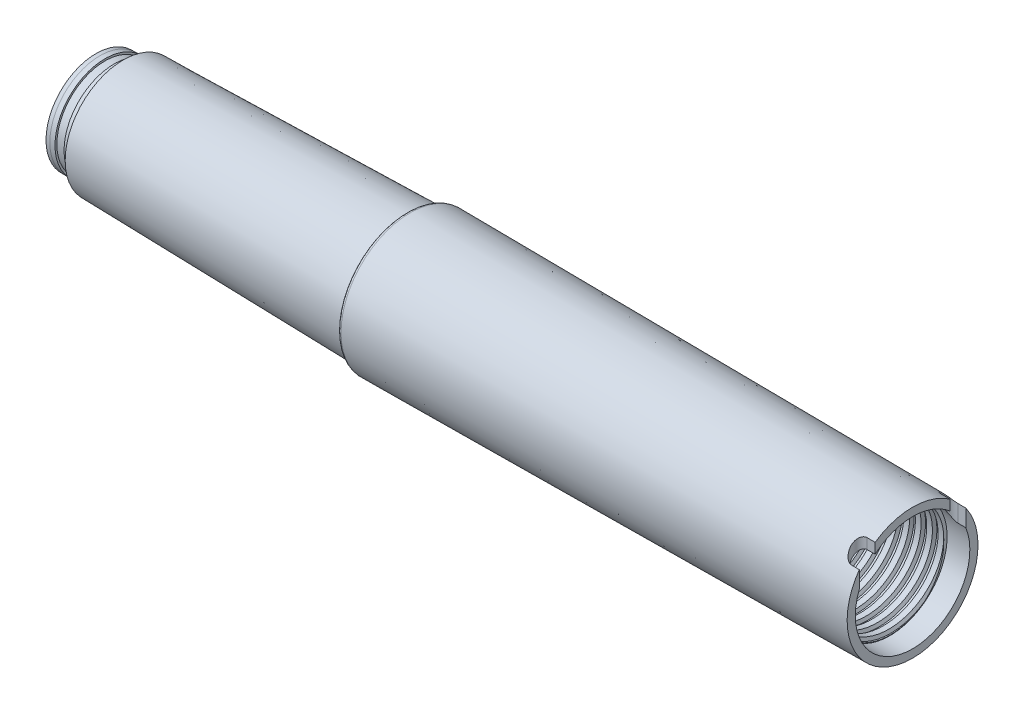
SolidWorks part; units mm, degrees
material "3.0205 (EN-AW 1200)"
ref_plane "Plano frontal" through (0, 0, 0) normal (0, 0, 1) x (1, 0, 0)
ref_plane "Plano superior" through (0, 0, 0) normal (0, 1, 0) x (1, 0, 0)
ref_plane "Plano direito" through (0, 0, 0) normal (1, 0, 0) x (0, 0, -1)
sketch "Esboço1" plane through (0, 0, 0) normal (0, 0, 1) x (1, 0, 0)
  line L0 (0, 0) -> (72, 0) construction
  line L1 (70, -4.75) -> (60, -4.75)
  line L2 (60, -4.75) -> (3, -4.75)
  line L3 (70, -4.75) -> (70, -5.05)
  line L4 (70, -5.05) -> (72, -5.05)
  line L5 (0, -3.45) -> (0.2, -3.25)
  line L6 (72, -5.77) -> (27.7022, -6.1)
  line L7 (27.4, -5.65) -> (27.4, -5.8)
  line L8 (2.4, -5.12) -> (27.4, -5.65)
  line L17 (3, -3.5387) -> (3, -4.75)
  line L18 (0, -4.41) -> (0.35, -4.42)
  line L19 (72, -5.77) -> (72, -5.05)
  line L21 (2.5, -3.25) -> (3, -3.5387)
  line L22 (0.2, -3.25) -> (2.5, -3.25)
  line L24 (2.4, -4.42) -> (2.4, -5.12)
  line L25 (1.6, -4.42) -> (2.4, -4.42)
  line L26 (1.6, -4.25) -> (1.6, -4.42)
  line L27 (0.8, -4.25) -> (1.6, -4.25)
  line L28 (0.8, -4.42) -> (0.8, -4.25)
  line L29 (0.35, -4.42) -> (0.8, -4.42)
  line L30 (0, -3.45) -> (0, -4.41)
  arc A0 (27.7022, -6.1) -> (27.4, -5.8) centre (27.7, -5.8) cw
  point P18 (27.4, -5.65)
  point P30 (0, -3.25)
  dimension "D19" = 0.3
  dimension "D29" = 10.24
  dimension "D2" = 11.54
  dimension "D3" = 72
  dimension "D4" = 6.5
  dimension "D5" = 8.82
  dimension "D6" = 8.84
  dimension "D7" = 0.35
  dimension "D8" = 0.8
  dimension "D9" = 0.8
  dimension "D10" = 2.4
  dimension "D11" = 3
  dimension "D12" = 8.5
  dimension "D13" = 12
  dimension "D14" = 30
  dimension "D15" = 0.5
  dimension "D16" = 0.9
  dimension "D17" = 11.3
  dimension "D18" = 9.5
  dimension "D20" = 2
  dimension "D21" = 10.1
  dimension "D22" = 27.4
  dimension "D23" = 0.2
  dimension "D24" = 45
  dimension "D25" = 12.2
  dimension "D27" = 9.5
  dimension "D28" = 0.3826
revolve "Revolução1" add sketch "Esboço1" angle 360 about L0
sketch "Esboço7" plane through (0, 0, 0) normal (0, 1, 0) x (1, 0, 0)
  line L0 (0, 0) -> (74.2533, 0) construction
  line L2 (72, -5.77) -> (72, 5.77) construction
  line L4 (71.3, -3.3) -> (73.3469, -3.3)
  line L5 (66.5566, -4) -> (75.5948, -4) construction
  line L6 (71.3, -3.3) -> (73.3469, -3.3)
  line L7 (71.3, -4.7) -> (73.3469, -4.7)
  line L8 (73.3469, -3.3) -> (73.3469, -4.7)
  line L9 (71.3, -3.3) -> (73.3469, -3.3)
  line L10 (71.3, -4.7) -> (73.3469, -4.7)
  line L13 (71.3, -3.3) -> (73.3469, -3.3)
  line L14 (71.3, -4.7) -> (73.3469, -4.7)
  line L15 (71.3, -3.3) -> (73.3469, -3.3)
  line L16 (71.3, -4.7) -> (73.3469, -4.7)
  line L18 (71.3, -4.7) -> (73.3469, -4.7)
  line L19 (71.3, -3.3) -> (73.3469, -3.3)
  line L20 (71.3, -4.7) -> (73.3469, -4.7)
  line L23 (71.3, -3.3) -> (73.3469, -3.3)
  line L24 (71.3, -4.7) -> (73.3469, -4.7)
  line L25 (71.3, -3.3) -> (73.3469, -3.3)
  line L26 (71.3, -4.7) -> (73.3469, -4.7)
  line L28 (71.3, 4.7) -> (73.3469, 4.7)
  line L29 (71.3, 3.3) -> (73.3469, 3.3)
  line L30 (73.3469, 3.3) -> (73.3469, 4.7)
  arc A0 (71.3, -3.3) -> (71.3, -4.7) centre (71.3, -4) ccw
  arc A1 (71.3, 3.3) -> (71.3, 4.7) centre (71.3, 4) cw
  dimension "D2" = 1.4
  dimension "D1" = 1.4
  dimension "D3" = 4
extrude "Extrusão1" cut sketch "Esboço7" along normal through all contours L4 A0 L7 L8 | A1 L29 L30 L28 region at (72.0439, 0, 4) region at (72.0439, 0, -4)
ref_plane "Plano1" through (64, 0, 0) normal (1, 0, 0) x (0, 0, -1)
sketch "Esboço3" plane through (64, 0, 0) normal (1, 0, 0) x (0, 0, -1)
  circle A1 centre (0, 0) radius 4.75
  dimension "D1" = 9.5
sketch "Esboço4" plane through (0, 0, 0) normal (0, 0, 1) x (1, 0, 0)
  line L0 (63.895, -5) -> (64.105, -5)
  line L2 (64, -4.3937) -> (64, -5.1464) construction
  line L3 (72, -5.05) -> (72, 1.8473) construction
  line L6 (63.75, -4.75) -> (64.25, -4.75)
  line L8 (58.2501, 0) -> (73.1599, 0) construction
  line L11 (63.895, -5) -> (63.75, -4.75)
  line L12 (64.105, -5) -> (64.25, -4.75)
  dimension "D1" = 10
  dimension "D2" = 8
  dimension "D3" = 4.75
  dimension "D4" = 0.5
  dimension "D5" = 0.25
  dimension "D7" = 0.21
curve "Hélice/Espiral2" pitch 1 height 6.75 radius 4.75 centre (64, 0, 0) axis (1, 0, 0) start towards (0, 0, -1)
sweep "Varredura de corte1" cut profiles "Esboço4" path "Hélice/Espiral2" align with end faces yes
